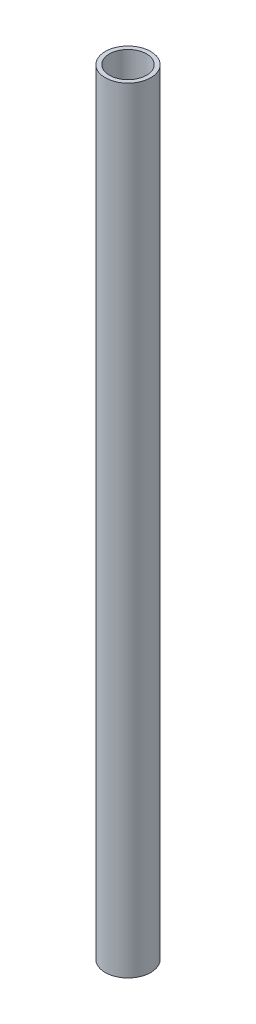
SolidWorks part; units mm, degrees
material "1060-H12 Rod (SS)"
ref_plane "Front Plane" through (0, 0, 0) normal (0, 0, 1) x (1, 0, 0)
ref_plane "Top Plane" through (0, 0, 0) normal (0, 1, 0) x (1, 0, 0)
ref_plane "Right Plane" through (0, 0, 0) normal (1, 0, 0) x (0, 0, -1)
sketch "Sketch1" plane through (0, 0, 0) normal (0, 1, 0) x (1, 0, 0)
  circle A0 centre (0, 0) radius 14.1
  circle A1 centre (0, 0) radius 11.5
  dimension "D1" = 28.2
  dimension "D2" = 2.6
extrude "Boss-Extrude1" add sketch "Sketch1" along normal blind 480.44
ref_point "Point1"
ref_point "Point2"
ref_axis "Axis1" through (0, 0, 0) along (0, 1, 0)
